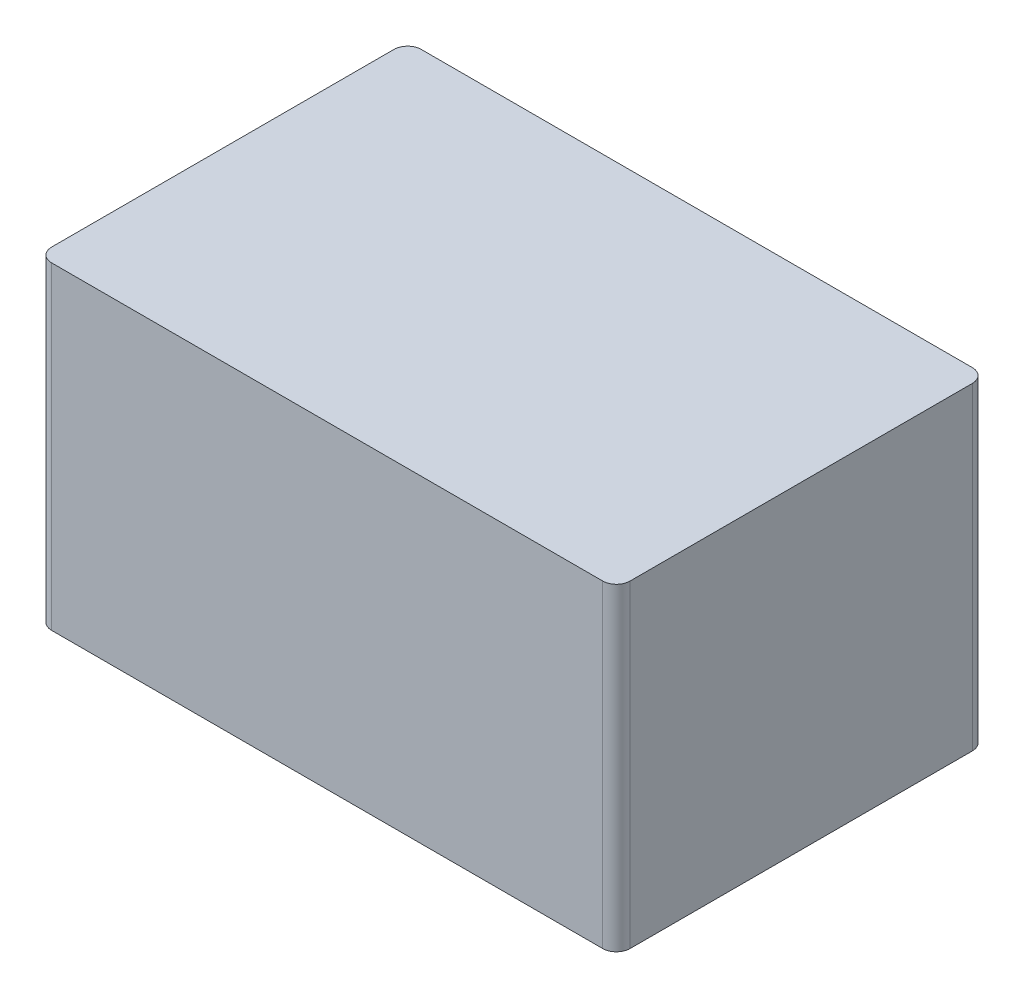
SolidWorks part; units mm, degrees
ref_plane "Front Plane" through (0, 0, 0) normal (0, 0, 1) x (1, 0, 0)
ref_plane "Top Plane" through (0, 0, 0) normal (0, 1, 0) x (1, 0, 0)
ref_plane "Right Plane" through (0, 0, 0) normal (1, 0, 0) x (0, 0, -1)
sketch "Sketch1" plane through (0, 0, 0) normal (0, 1, 0) x (1, 0, 0)
  line L1 (0, 0) -> (84.5, 0)
  line L2 (0, 0) -> (0, 54)
  line L3 (0, 54) -> (84.5, 54)
  line L4 (84.5, 0) -> (84.5, 54)
  dimension "D1" = 84.5
  dimension "D2" = 54
extrude "Boss-Extrude2" add sketch "Sketch1" along normal blind 46.5
fillet "Fillet1" radius 2 4 edges at (0, 23.25, -54) (0, 23.25, 0) (84.5, 23.25, -54) (84.5, 23.25, 0)
